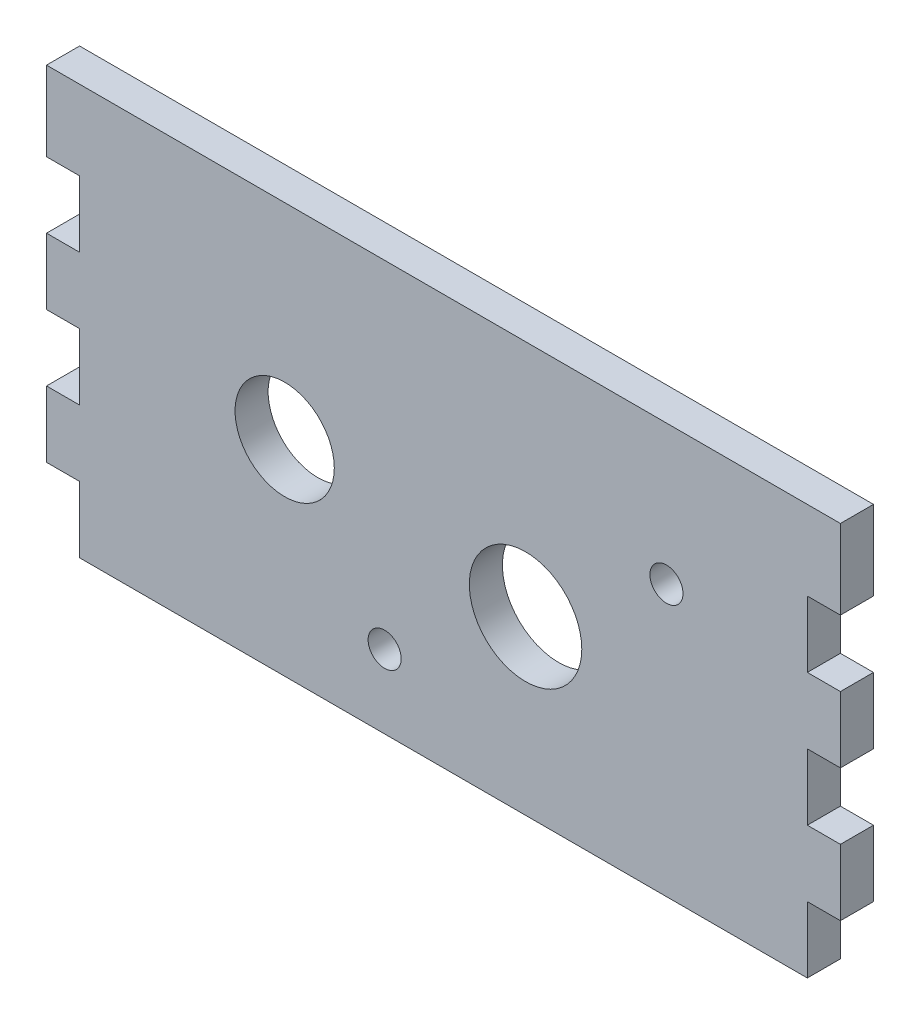
SolidWorks part; units mm, degrees
ref_plane "정면" through (0, 0, 0) normal (0, 0, 1) x (1, 0, 0)
ref_plane "윗면" through (0, 0, 0) normal (0, 1, 0) x (1, 0, 0)
ref_plane "우측면" through (0, 0, 0) normal (1, 0, 0) x (0, 0, -1)
sketch "스케치2" plane through (0, 0, 0) normal (0, 0, 1) x (1, 0, 0)
  line L0 (-6.0717, -5) -> (65.5766, -5) construction
  line L1 (-60, -31) -> (60, -31)
  line L2 (-60, -31) -> (-60, 31)
  line L3 (-60, 31) -> (60, 31)
  line L4 (60, -31) -> (60, 31)
  line L5 (-60, -31) -> (60, 31) construction
  line L6 (-60, 31) -> (60, -31) construction
  line L7 (-15.8273, -24.7708) -> (37.7136, 12.7189) construction
  circle A0 centre (12.4083, -5) radius 8.5
  circle A1 centre (-24, 0) radius 7.5
  circle A2 centre (33.7062, 9.913) radius 2.5
  circle A3 centre (-8.8897, -19.913) radius 2.5
  point P0 (0, 0)
  point P14 (0, 0)
  point P17 (31.9009, 12.2058)
  point P20 (-13.5917, -27.6303)
  point P21 (0, 0)
  dimension "D5" = 17
  dimension "D8" = 15
  dimension "D9" = 35
  dimension "D10" = 5
  dimension "D1" = 62
  dimension "D2" = 120
  dimension "D3" = 36.75
  dimension "D4" = 36
  dimension "D6" = 31
  dimension "D7" = 36
  dimension "D11" = 26
  dimension "D12" = 26
extrude "보스-돌출1" add sketch "스케치2" along normal blind 5 contours L1 L4 L3 L2 A1 A0 region at (0.134, 0.1903, 0)
sketch "스케치3" plane through (0, 0, 5) normal (0, 0, 1) x (1, 0, 0)
  line L0 (-60, -31) -> (-60, 31) construction
  line L1 (-60, -21) -> (-55, -21)
  line L2 (-60, -21) -> (-60, -31)
  line L3 (-60, -31) -> (-55, -31)
  line L4 (-55, -21) -> (-55, -31)
  line L5 (-60, -31) -> (60, -31) construction
  dimension "D1" = 5
  dimension "D2" = 10
extrude "컷-돌출1" cut sketch "스케치3" against normal up to next
pattern_linear "선형 패턴1" count 3 spacing 20 along (0, 1, 0) of "컷-돌출1"
mirror "대칭 복사1" about plane through (0, 0, 0) normal (1, 0, 0) of "선형 패턴1"
